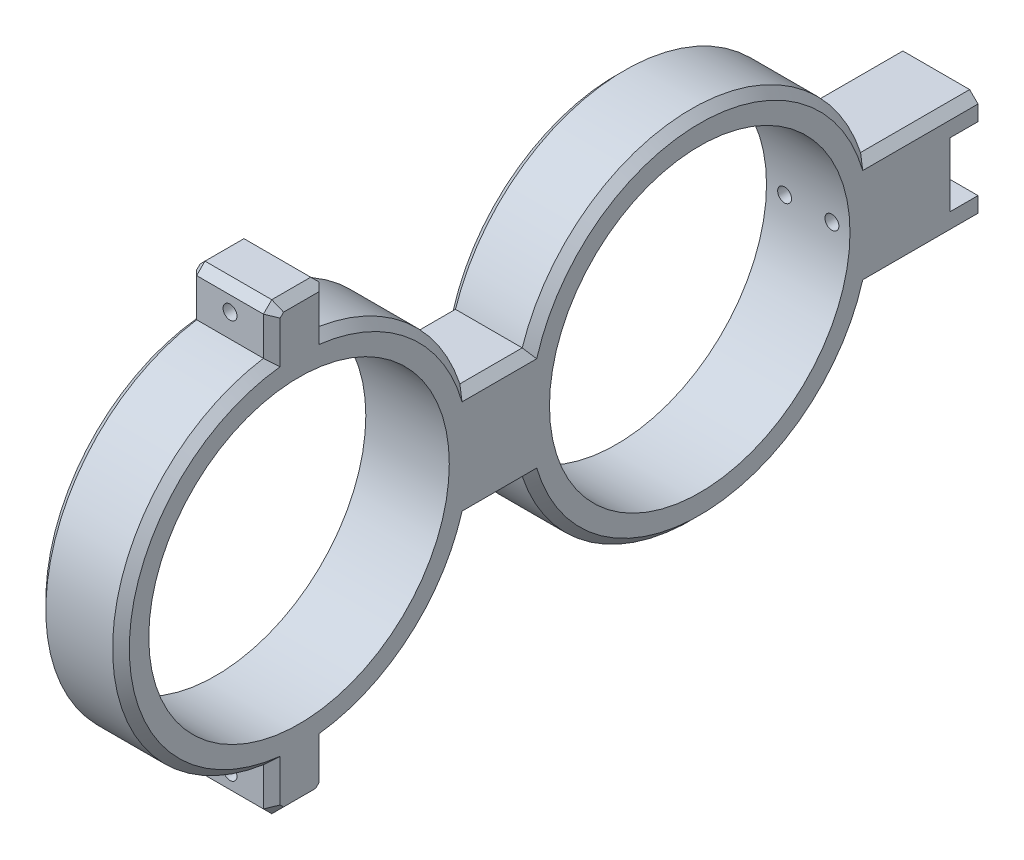
SolidWorks part; units mm, degrees
ref_plane "前视基准面" through (0, 0, 0) normal (0, 0, 1) x (1, 0, 0)
ref_plane "上视基准面" through (0, 0, 0) normal (0, 1, 0) x (1, 0, 0)
ref_plane "右视基准面" through (0, 0, 0) normal (1, 0, 0) x (0, 0, -1)
sketch "草图2" plane through (0, 0, 0) normal (1, 0, 0) x (0, 0, -1)
  circle A0 centre (0, 0) radius 32
  dimension "D1" = 64
extrude "凸台-拉伸1" add sketch "草图2" along normal blind 15
sketch "草图3" plane through (15, 0, 0) normal (1, 0, 0) x (0, 0, -1)
  circle A0 centre (0, 0) radius 27
  dimension "D1" = 54
extrude "切除-拉伸1" cut sketch "草图3" against normal through all
sketch "草图4" plane through (15, 0, 0) normal (1, 0, 0) x (0, 0, -1)
  line L1 (25.0799, 10) -> (117, 10)
  line L2 (25.0799, 10) -> (25.0799, -10)
  line L3 (25.0799, -10) -> (117, -10)
  line L4 (117, 10) -> (117, -10)
  line L5 (25.0799, 10) -> (117, -10) construction
  line L6 (25.0799, -10) -> (117, 10) construction
  circle A0 centre (0, 0) radius 27 construction
  circle A1 centre (0, 0) radius 32 construction
  point P0 (71.0399, 0)
  dimension "D1" = 117
  dimension "D2" = 20
extrude "凸台-拉伸2" add sketch "草图4" against normal blind 15
sketch "草图5" plane through (15, 0, 0) normal (1, 0, 0) x (0, 0, -1)
  circle A0 centre (0, 0) radius 27
  dimension "D1" = 54
extrude "切除-拉伸2" cut sketch "草图5" against normal through all
sketch "草图6" plane through (0, 0, -117) normal (0, 0, -1) x (-1, 0, 0)
  line L0 (0, 10) -> (-15, 10) construction
  line L1 (0, 5.75) -> (-15, 5.75)
  line L2 (0, 5.75) -> (0, 10)
  line L3 (0, 10) -> (-15, 10)
  line L4 (-15, 5.75) -> (-15, 10)
  line L5 (0, 5.75) -> (-15, 10) construction
  line L6 (0, 10) -> (-15, 5.75) construction
  line L7 (-15, -10) -> (-15, 10) construction
  line L8 (0, -10) -> (0, 10) construction
  line L9 (-15, 0) -> (0, 0) construction
  line L10 (0, -10) -> (-15, -10)
  line L11 (-15, -5.75) -> (-15, -10)
  line L12 (0, -5.75) -> (-15, -5.75)
  line L13 (0, -5.75) -> (0, -10)
  point P0 (-7.5, 7.875)
  dimension "D1" = 11.5
extrude "凸台-拉伸3" add sketch "草图6" along normal blind 5
sketch "草图8" plane through (15, 0, 0) normal (1, 0, 0) x (0, 0, -1)
  line L0 (-32, 0) -> (117, 0) construction
  line L1 (5.0998, 26.5516) -> (-4.9002, 26.5516)
  line L2 (5.0998, 26.5516) -> (5.0998, 40)
  line L3 (5.0998, 40) -> (-4.9002, 40)
  line L4 (-4.9002, 26.5516) -> (-4.9002, 40)
  line L5 (5.0998, 26.5516) -> (-4.9002, 40) construction
  line L6 (5.0998, 40) -> (-4.9002, 26.5516) construction
  line L7 (117, -5.75) -> (117, 5.75) construction
  line L8 (5.0998, -40) -> (-4.9002, -40)
  line L9 (-4.9002, -26.5516) -> (-4.9002, -40)
  line L10 (5.0998, -26.5516) -> (-4.9002, -26.5516)
  line L11 (5.0998, -26.5516) -> (5.0998, -40)
  line L12 (0.0998, 50.6797) -> (0.0998, -34.5244) construction
  circle A0 centre (0, 0) radius 27 construction
  arc A1 (30.3974, 10) -> (30.3974, -10) centre (0, 0) ccw construction
  arc A2 (30.3974, 10) -> (30.3974, -10) centre (0, 0) ccw construction
  point P0 (0.0998, 33.2758)
  dimension "D1" = 10
  dimension "D2" = 40
extrude "凸台-拉伸4" add sketch "草图8" against normal blind 15
sketch "草图9" plane through (0, 0, 4.9002) normal (0, 0, 1) x (1, 0, 0)
  line L0 (0, 35.8113) -> (15, 35.8113) construction
  line L1 (0, 40) -> (0, 31.6226) construction
  line L2 (15, 40) -> (15, 31.6226) construction
  line L3 (7.5, 40) -> (7.5, 31.6226) construction
  line L4 (0, 40) -> (15, 40) construction
  line L5 (15, 31.6226) -> (0, 31.6226) construction
  line L6 (0, 0) -> (28.5789, 0) construction
  circle A1 centre (7.5, 35.8113) radius 1.25
  circle A2 centre (7.5, -35.8113) radius 1.25
  point P12 (7.5, 35.8113)
  dimension "D1" = 2.5
extrude "切除-拉伸4" cut sketch "草图9" against normal up to next
sketch "草图10" plane through (15, 0, 0) normal (1, 0, 0) x (0, 0, -1)
  circle A0 centre (0, 0) radius 27
  dimension "D1" = 54
extrude "切除-拉伸5" cut sketch "草图10" against normal through all
chamfer "倒角2" distance 1.5 angle 45 4 edges at (7.5, -40, 4.9002) (7.5, -40, -5.0998) (7.5, 40, -5.0998) (7.5, 40, 4.9002)
chamfer "倒角3" distance 1.5 angle 45 25 edges at (0, -24.3402, -20.7739) (15, -35.0455, -5.0998) (0, -35.0455, -5.0998) (0, -39.25, -4.3498) (15, -40, -0.0998) (0, -40, -0.0998) (0, -39.25, 4.1502) (0, -35.0613, 4.9002) (15, -35.0613, 4.9002) (0, 24.3402, -20.7739) (0, 35.0455, -5.0998) (15, 35.0455, -5.0998) (0, 39.25, -4.3498) (15, 40, -0.0998) (0, 40, -0.0998) (0, 39.25, 4.1502) (15, 35.0613, 4.9002) (0, 35.0613, 4.9002) (0, 0, 32) (15, 24.3402, -20.7739) (15, -24.3402, -20.7739) (15, -39.25, -4.3498) (15, -39.25, 4.1502) (15, 39.25, 4.1502) (15, 0, 32)
sketch "草图13" plane through (15, 0, 0) normal (1, 0, 0) x (0, 0, -1)
  line L0 (117, 0) -> (27, 0) construction
  line L1 (117, -5.75) -> (117, 5.75) construction
  circle A0 centre (72, 0) radius 32
  circle A1 centre (0, 0) radius 27 construction
  dimension "D1" = 64
extrude "凸台-拉伸5" add sketch "草图13" against normal blind 15
sketch "草图14" plane through (15, 0, 0) normal (1, 0, 0) x (0, 0, -1)
  circle A0 centre (72, 0) radius 27
  arc A1 (102.3974, 10) -> (41.6026, 10) centre (72, 0) ccw construction
  dimension "D1" = 54
extrude "切除-拉伸8" cut sketch "草图14" against normal through all
chamfer "倒角4" distance 1.5 angle 45 16 edges at (0, -10, -35.2083) (0, 10, -112.1987) (15, -10, -35.2083) (15, 10, -112.1987) (15, 10, -35.2083) (0, 10, -35.2083) (0, -10, -112.1987) (15, -10, -112.1987) (0, -32, -72) (15, -32, -72) (0, 32, -72) (15, 32, -72)
sketch "草图7" plane through (0, 0, -117) normal (0, 0, -1) x (-1, 0, 0)
  line L0 (-7.5, -5.75) -> (-7.5, 5.75) construction
  line L3 (0, -5.75) -> (-15, -5.75) construction
  line L4 (-15, 5.75) -> (0, 5.75) construction
  line L5 (-15, 0) -> (0, 0) construction
  line L6 (-15, -5.75) -> (-15, 5.75) construction
  line L7 (0, -5.75) -> (0, 5.75) construction
  circle A1 centre (-3.25, 0) radius 1.25
  circle A2 centre (-11.75, 0) radius 1.25
  dimension "D1" = 2.5
  dimension "D2" = 8.5
extrude "切除-拉伸3" cut sketch "草图7" against normal blind 30
sketch "草图11" plane through (0, 0, 0) normal (0, 0, 1) x (1, 0, 0)
  line L1 (60.6516, -49.0819) -> (-27.9407, -49.0819)
  line L2 (60.6516, -49.0819) -> (60.6516, 47.2432)
  line L3 (60.6516, 47.2432) -> (-27.9407, 47.2432)
  line L4 (-27.9407, -49.0819) -> (-27.9407, 47.2432)
  line L5 (60.6516, -49.0819) -> (-27.9407, 47.2432) construction
  line L6 (60.6516, 47.2432) -> (-27.9407, -49.0819) construction
  point P0 (16.3554, -0.9194)
extrude "切除-拉伸9" [suppressed] cut sketch "草图11" along normal through all
sketch "草图16" [suppressed] plane through (0, 0, 0) normal (0, 0, 1) x (1, 0, 0)
  circle A0 centre (-7.5, 35.8113) radius 1.5
  circle A3 centre (7.5, -35.8113) radius 1.5
  circle A4 centre (-7.5, 35.8113) radius 1.25 construction
  point P3 (-7.5, 35.8113)
  dimension "D1" = 3
extrude "切除-拉伸10" [suppressed] cut sketch "草图16" against normal up to next
